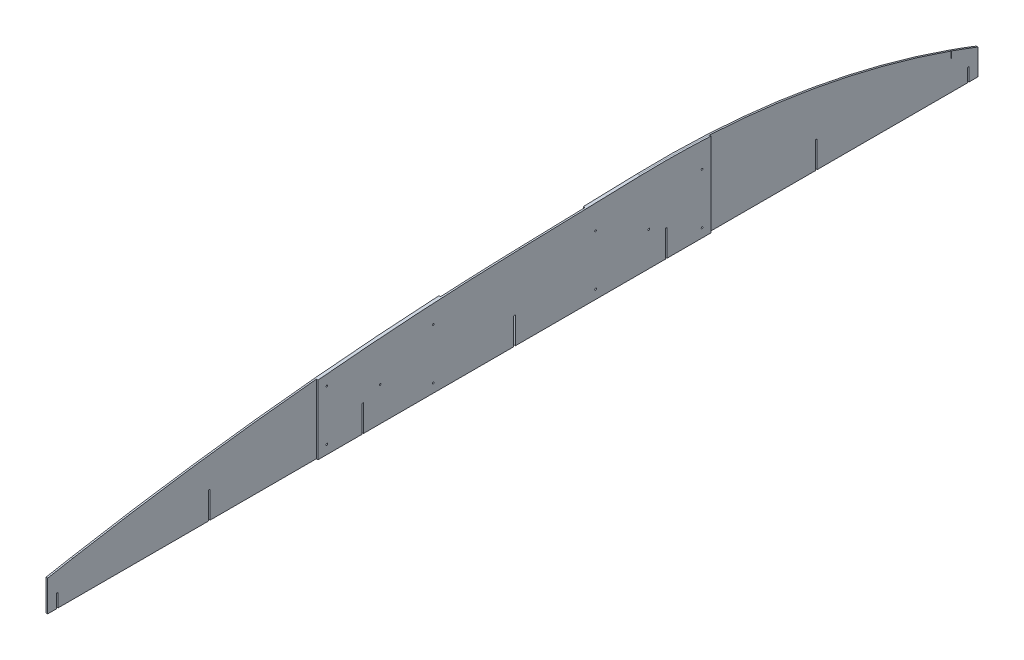
SolidWorks part; units mm, degrees
material "Oak"
ref_plane "Front Plane" through (0, 0, 0) normal (0, 0, 1) x (1, 0, 0)
ref_plane "Top Plane" through (0, 0, 0) normal (0, 1, 0) x (1, 0, 0)
ref_plane "Right Plane" through (0, 0, 0) normal (1, 0, 0) x (0, 0, -1)
sketch "Sketch1" plane through (0, 0, 0) normal (1, 0, 0) x (0, 0, -1)
  line L0 (-1117.6, 0) -> (-867.643, 0)
  line L2 (35.032, 463.4393) -> (716.7743, 482.1841)
  line L3 (-1117.6, 392.5753) -> (-1117.6, 0)
  line L5 (-858.245, 0) -> (-4.699, 0)
  line L6 (4.699, 0) -> (858.245, 0)
  line L7 (867.643, 0) -> (1117.6, 0)
  line L8 (1117.6, 0) -> (1117.6, 476.9203)
  line L12 (4.699, 0) -> (4.699, 152.4)
  line L13 (4.699, 152.4) -> (-4.699, 152.4)
  line L14 (-4.699, 152.4) -> (-4.699, 0)
  line L15 (-858.245, 0) -> (-858.245, 152.4)
  line L16 (-858.245, 152.4) -> (-867.643, 152.4)
  line L17 (-867.643, 152.4) -> (-867.643, 0)
  line L18 (858.245, 0) -> (858.245, 152.4)
  line L19 (858.245, 152.4) -> (867.643, 152.4)
  line L20 (867.643, 152.4) -> (867.643, 0)
  line L22 (-4.699, 0) -> (4.699, 0) construction
  arc A5 (35.032, 463.4393) -> (-1117.6, 392.5753) centre (503.0671, -16558.7955) ccw
  arc A6 (1117.6, 476.9203) -> (716.7743, 482.1841) centre (852.4299, -4451.5504) ccw
  circle A7 centre (-1066.8, 337.9336) radius 4.7625
  circle A8 centre (-1066.8, 50.8) radius 4.7625
  circle A9 centre (-461.243, 50.8) radius 4.7625
  circle A10 centre (-461.243, 337.9336) radius 4.7625
  circle A11 centre (-764.0215, 194.3668) radius 4.7625
  circle A18 centre (1066.8, 337.9336) radius 4.7625
  circle A19 centre (1066.8, 50.8) radius 4.7625
  circle A20 centre (461.243, 50.8) radius 4.7625
  circle A21 centre (461.243, 337.9336) radius 4.7625
  circle A22 centre (764.0215, 194.3668) radius 4.7625
  dimension "D1" = 2235.2
extrude "Boss-Extrude1" add sketch "Sketch1" along normal blind 9.398
sketch "Sketch2" plane through (0, 0, 0) normal (1, 0, 0) x (0, 0, -1)
  line L0 (-2498.7725, 203.2) -> (-2498.3587, 188.1501)
  line L1 (-2645.643, 176.2324) -> (-2645.643, 0)
  line L2 (-2645.643, 0) -> (-2594.843, 0)
  line L3 (-2585.445, 0) -> (-1731.243, 0)
  line L4 (-1721.845, 0) -> (-867.643, 0)
  line L5 (-858.245, 0) -> (-410.443, 0)
  line L6 (-410.443, 0) -> (-410.443, 445.352)
  line L7 (-2499.1518, 203.1321) -> (-2498.7396, 188.1396)
  line L8 (-1117.6, 0) -> (-867.643, 0)
  line L9 (-858.245, 0) -> (-410.443, 0)
  line L10 (-2585.445, 0) -> (-2585.445, 76.2)
  line L11 (-2585.445, 76.2) -> (-2594.843, 76.2)
  line L12 (-2594.843, 76.2) -> (-2594.843, 0)
  line L13 (-1721.845, 0) -> (-1721.845, 152.4)
  line L14 (-1721.845, 152.4) -> (-1731.243, 152.4)
  line L15 (-1731.243, 152.4) -> (-1731.243, 0)
  line L16 (-858.245, 0) -> (-858.245, 152.4)
  line L17 (-858.245, 152.4) -> (-867.643, 152.4)
  line L18 (-867.643, 152.4) -> (-867.643, 0)
  line L19 (-2499.1534, 203.1895) -> (-2498.7396, 188.1396) construction
  line L20 (-2498.7396, 188.1396) -> (-2498.3587, 188.1501)
  arc A0 (-410.443, 445.352) -> (-2498.7725, 203.2) centre (503.0671, -16558.7955) ccw
  circle A1 centre (-1066.8, 337.9336) radius 4.7625
  circle A2 centre (-1066.8, 50.8) radius 4.7625
  circle A3 centre (-461.243, 50.8) radius 4.7625
  circle A4 centre (-461.243, 337.9336) radius 4.7625
  circle A5 centre (-764.0215, 194.3668) radius 4.7625
  circle A6 centre (-1066.8, 337.9336) radius 4.7625
  circle A7 centre (-1066.8, 50.8) radius 4.7625
  circle A8 centre (-461.243, 50.8) radius 4.7625
  circle A9 centre (-461.243, 337.9336) radius 4.7625
  circle A10 centre (-764.0215, 194.3668) radius 4.7625
  arc A11 (-2499.1518, 203.1321) -> (-2645.643, 176.2324) centre (503.0671, -16558.7955) ccw
  dimension "D1" = 0.381
extrude "Boss-Extrude2" add sketch "Sketch2" against normal blind 9.398 contours L7 A11 L1 L2 L12 L11 L10 L3 L15 L14 L13 L4 L18 L17 L16 L5 L6 A0 L0 L20 A1 A2 A3 A4 A5 region at (0, 177.5726, 1378.3459)
sketch "Sketch3" plane through (0, 0, 0) normal (1, 0, 0) x (0, 0, -1)
  line L0 (410.443, 473.7614) -> (716.7743, 482.1842)
  line L1 (410.443, 0) -> (858.245, 0)
  line L2 (867.643, 0) -> (1117.6, 0)
  line L3 (410.443, 473.7614) -> (716.7743, 482.1842)
  line L4 (2645.643, 146.7673) -> (2645.643, 0)
  line L5 (2493.243, 203.3257) -> (2493.243, 167.188)
  line L6 (410.443, 473.7614) -> (410.443, 0)
  line L7 (410.443, 0) -> (858.245, 0)
  line L8 (867.643, 0) -> (1721.845, 0)
  line L9 (1731.243, 0) -> (2585.445, 0)
  line L10 (2594.843, 0) -> (2645.643, 0)
  line L11 (2585.445, 0) -> (2585.445, 76.2)
  line L12 (2585.445, 76.2) -> (2594.843, 76.2)
  line L13 (2594.843, 76.2) -> (2594.843, 0)
  line L14 (1721.845, 0) -> (1721.845, 152.4)
  line L15 (1721.845, 152.4) -> (1731.243, 152.4)
  line L16 (1731.243, 152.4) -> (1731.243, 0)
  line L17 (858.245, 0) -> (858.245, 152.4)
  line L18 (858.245, 152.4) -> (867.643, 152.4)
  line L19 (867.643, 152.4) -> (867.643, 0)
  line L20 (2493.624, 203.1914) -> (2493.624, 167.188)
  line L21 (2493.624, 203.3257) -> (2493.624, 167.188) construction
  line L22 (2493.243, 167.188) -> (2493.624, 167.188)
  circle A0 centre (1066.8, 337.9336) radius 4.7625
  circle A1 centre (1066.8, 50.8) radius 4.7625
  circle A2 centre (461.243, 50.8) radius 4.7625
  circle A3 centre (461.243, 337.9336) radius 4.7625
  circle A4 centre (764.0215, 194.3668) radius 4.7625
  arc A5 (2645.643, 146.7673) -> (2493.624, 203.1914) centre (852.4299, -4451.5504) ccw
  circle A6 centre (1066.8, 337.9336) radius 4.7625
  circle A7 centre (1066.8, 50.8) radius 4.7625
  circle A8 centre (461.243, 50.8) radius 4.7625
  circle A9 centre (461.243, 337.9336) radius 4.7625
  circle A10 centre (764.0215, 194.3668) radius 4.7625
  arc A11 (2493.243, 203.3257) -> (716.7743, 482.1842) centre (852.4299, -4451.5504) ccw
  dimension "D1" = 0.381
extrude "Boss-Extrude3" add sketch "Sketch3" against normal blind 9.398 contours L5 A11 L0 L6 L1 L17 L18 L19 L2 L8 L14 L15 L16 L9 L11 L12 L13 L10 L4 A5 L20 L22 A0 A1 A2 A3 A4 region at (0, 210.1722, -1378.0782)
